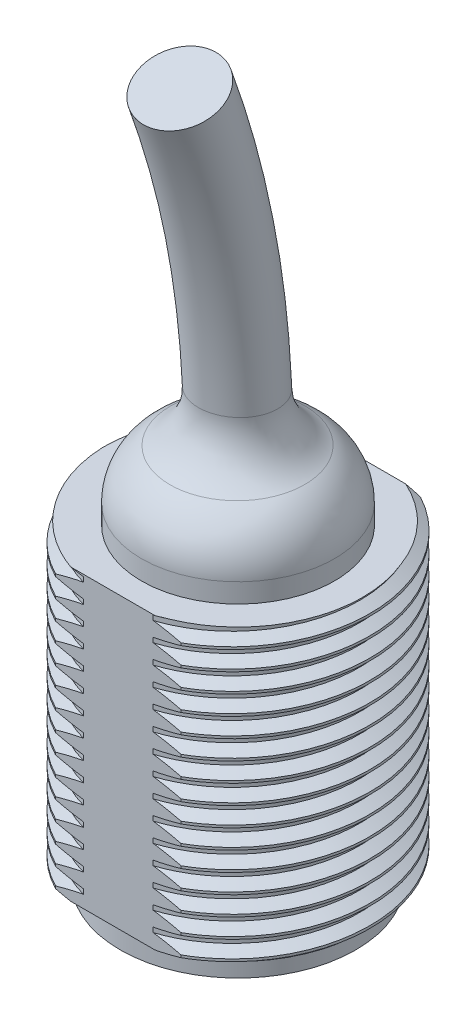
SolidWorks part; units mm, degrees
material "PEI"
ref_plane "Front Plane" through (0, 0, 0) normal (0, 0, 1) x (1, 0, 0)
ref_plane "Top Plane" through (0, 0, 0) normal (0, 1, 0) x (1, 0, 0)
ref_plane "Right Plane" through (0, 0, 0) normal (1, 0, 0) x (0, 0, -1)
sketch "Sketch1" plane through (0, 0, 0) normal (0, 1, 0) x (1, 0, 0)
  circle A0 centre (0, 0) radius 7
  dimension "D1" = 14
extrude "body" add sketch "Sketch1" along normal blind 15
ref_plane "Plane2" through (0, 17, 0) normal (0, 1, 0) x (1, 0, 0)
sketch "Sketch8" plane through (0, 0, 0) normal (0, -1, 0) x (1, 0, 0)
  circle A0 centre (0, 0) radius 6.1
  dimension "D1" = 12.2
extrude "socketLip" add sketch "Sketch8" along normal blind 1
sketch "Sketch9" plane through (0, 15, 0) normal (0, 1, 0) x (1, 0, 0)
  circle A0 centre (0, 0) radius 5
  dimension "D1" = 10
extrude "Boss-Extrude3" add sketch "Sketch9" along normal blind 4
fillet "Fillet1" radius 3 1 edges at (0, 19, 5)
sketch "Sketch10" plane through (0, 19, 0) normal (0, 1, 0) x (1, 0, 0)
  line L0 (11.774, -50) -> (-13.7487, -50) construction
  circle A1 centre (0, 0) radius 2
  circle A2 centre (0, 0) radius 2
  dimension "D2" = 50
  dimension "D1" = 0
revolve "Revolve1" add sketch "Sketch10" angle 20 about L0 reverse direction yes
fillet "Fillet2" radius 3 1 edges at (0, 19, 2)
sketch "Sketch11" plane through (0, -1, 0) normal (0, -1, 0) x (1, 0, 0)
  circle A0 centre (0, 0) radius 5.1
  dimension "D1" = 10.2
extrude "Cut-Extrude1" cut sketch "Sketch11" against normal blind 15.4
sketch "Sketch12" plane through (0, 14.4, 0) normal (0, -1, 0) x (1, 0, 0)
  circle A0 centre (0, 0) radius 3.05
  dimension "D1" = 6.1
extrude "Boss-Extrude4" add sketch "Sketch12" along normal blind 10.7
sketch "Sketch13" plane through (0, -1, 0) normal (0, -1, 0) x (1, 0, 0)
  line L0 (5.7, 0) -> (6.1, 0) construction
  line L1 (5.7, 1.3) -> (3.05, 1.3)
  line L2 (5.7, 1.3) -> (5.7, -1.3)
  line L3 (5.7, -1.3) -> (3.05, -1.3)
  line L4 (3.05, 1.3) -> (3.05, -1.3)
  circle A0 centre (0, 0) radius 6.1 construction
  circle A1 centre (0, 0) radius 3.05 construction
  point P4 (3.05, 0)
  dimension "D1" = 2.6
  dimension "D2" = 0.4
extrude "Cut-Extrude2" cut sketch "Sketch13" against normal up to surface (15.4 mm away) up to face at (0, 14.4, -3.05)
thread "Thread1" pitch 1 method cut profile "Thread Profile1" start angle 0, offset 0, length 20, pitch 1, diameter 14
ref_plane "Plane1" through (-7, 17, 0) normal (0, 0, 1) x (-1, 0, 0)
sketch "Thread Profile1" plane through (-7, 17, 0) normal (0, 0, 1) x (-1, 0, 0)
  line L0 (0, 0) -> (0, 1) construction
  line L11 (0, 0) -> (0, 0.875)
  line L12 (0, 0.875) -> (-0.5413, 0.5625)
  line L13 (-0.5413, 0.5625) -> (-0.5413, 0.3125)
  line L15 (-0.5413, 0.3125) -> (0, 0)
  line L17 (-0.5413, 0.4375) -> (0, 0.4375) construction
  point P2 (0, 0)
  dimension "Pitch" = 1
  dimension "Profile_Angle" = 60
  dimension "Profile_Land" = 0.25
  dimension "Profile_Height" = 0.5413
sketch "Sketch14" plane through (0, -1, 0) normal (0, -1, 0) x (1, 0, 0)
  line L0 (-9.2683, 0) -> (9.2683, 0) construction
  line L1 (10, 11.2) -> (-10, 11.2)
  line L2 (10, 11.2) -> (10, 6.2)
  line L3 (10, 6.2) -> (-10, 6.2)
  line L4 (-10, 11.2) -> (-10, 6.2)
  line L5 (-10, -11.2) -> (-10, -6.2)
  line L6 (10, -6.2) -> (-10, -6.2)
  line L7 (10, -11.2) -> (10, -6.2)
  line L8 (10, -11.2) -> (-10, -11.2)
  point P8 (0, 6.2)
  dimension "D1" = 20
  dimension "D2" = 5
  dimension "D3" = 12.4
extrude "Cut-Extrude3" cut sketch "Sketch14" against normal through all both and the other way through all
